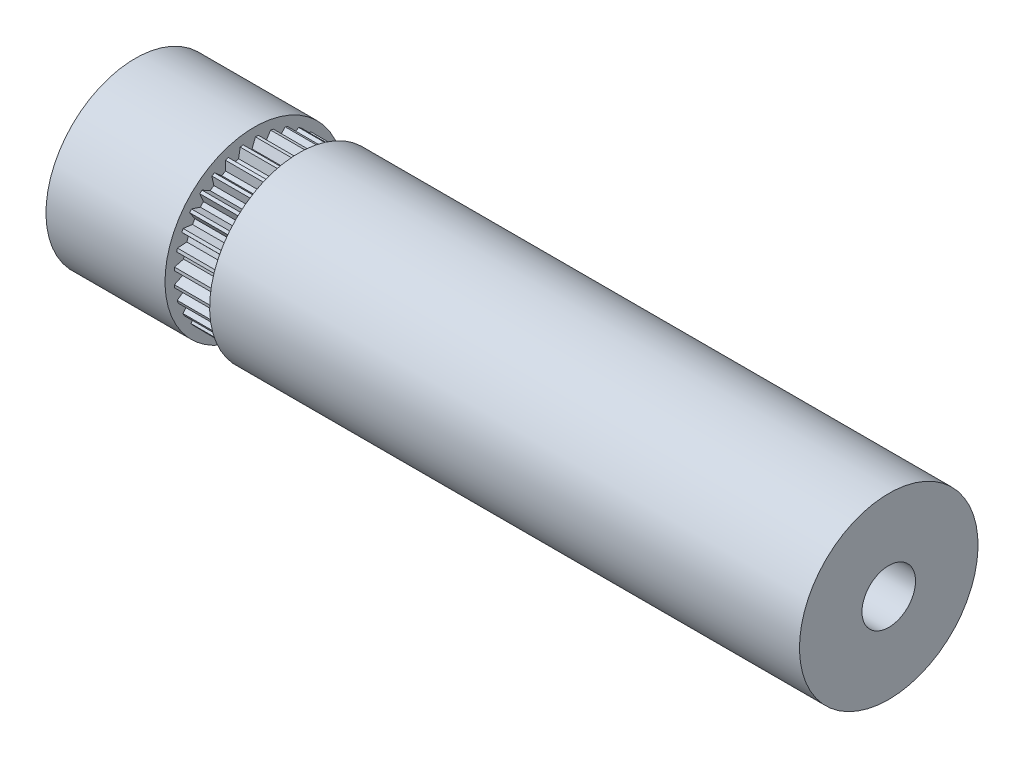
SolidWorks part; units mm, degrees
ref_plane "Plan de face" through (0, 0, 0) normal (0, 0, 1) x (1, 0, 0)
ref_plane "Plan de dessus" through (0, 0, 0) normal (0, 1, 0) x (1, 0, 0)
ref_plane "Plan de droite" through (0, 0, 0) normal (1, 0, 0) x (0, 0, -1)
sketch "Esquisse1" plane through (0, 0, 0) normal (0, 0, 1) x (1, 0, 0)
  line L0 (-81.1413, 0) -> (75.2437, 0) construction
  line L1 (-63.3, 15) -> (-63.3, 0)
  line L2 (63.3, 15) -> (63.3, 0)
  line L4 (-63.3, 15) -> (-43.3, 15)
  line L5 (-63.3, 0) -> (63.3, 0)
  line L6 (0, 15) -> (0, 0) construction
  line L10 (-35.8, 15) -> (63.3, 15)
  line L12 (-43.3, 15) -> (-43.3, 12)
  line L13 (-43.3, 12) -> (-35.8, 12)
  line L14 (-35.8, 15) -> (-35.8, 12)
  dimension "D1" = 63.3
  dimension "D4" = 15
  dimension "D6" = 7.5
  dimension "D7" = 3
revolve "Révolution1" add sketch "Esquisse1" angle 360 about L5
sketch "Esquisse3" plane through (-43.3, 0, 0) normal (1, 0, 0) x (0, 0, -1)
  line L0 (0, 0) -> (0.4912, 14.992) construction
  line L1 (-1.5159, 11.3463) -> (2.4996, 11.2147) construction
  line L2 (0.6911, 13.4545) -> (1.3692, 11.2518)
  line L3 (0.1911, 13.4709) -> (-0.6297, 11.3172)
  line L4 (-0.6297, 11.3172) -> (1.3692, 11.2518)
  line L5 (0.6911, 13.4545) -> (0.1911, 13.4709)
  circle A0 centre (0, 0) radius 15 construction
  point P7 (3.1073, 11.2147)
  point P12 (0.4649, 14.1893)
  point P13 (0, 0)
  dimension "D1" = 0.5
  dimension "D2" = 1
extrude "Boss.-Extru.1" add sketch "Esquisse3" along normal up to surface (7.5 mm away) up to face at (-35.8, -12, 0)
pattern_circular "Répétition circulaire1" count 33 over 360 about axis through (-63.3, 0, 0) along (-1, 0, 0) of "Boss.-Extru.1"
sketch "Esquisse7" plane through (-63.3, 0, 0) normal (-1, 0, 0) x (0, 0, 1)
  circle A0 centre (0, 0) radius 4.5
extrude "Enlèv. mat.-Extru.3" cut sketch "Esquisse7" along normal through all and the other way through all
